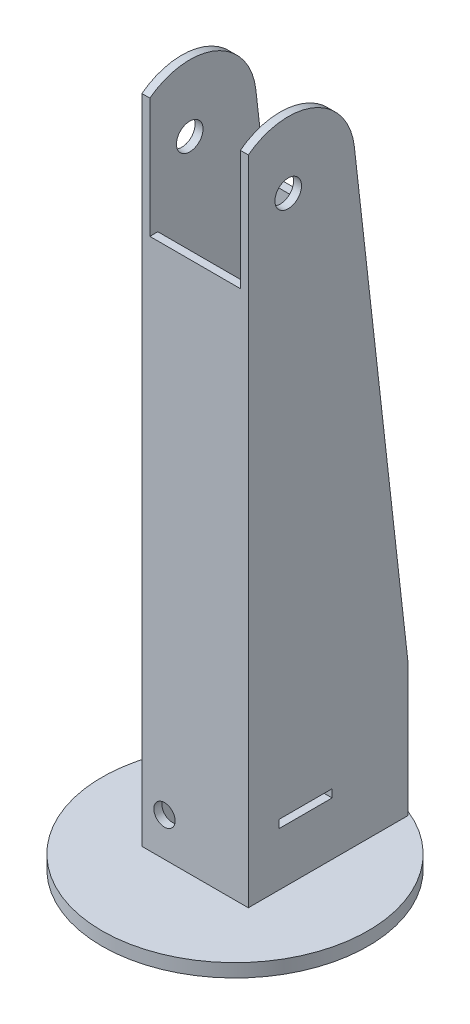
SolidWorks part; units mm, degrees
ref_plane "Alzado" through (0, 0, 0) normal (0, 0, 1) x (1, 0, 0)
ref_plane "Planta" through (0, 0, 0) normal (0, 1, 0) x (1, 0, 0)
ref_plane "Vista lateral" through (0, 0, 0) normal (1, 0, 0) x (0, 0, -1)
sketch "Croquis1" plane through (0, 0, 0) normal (0, 1, 0) x (1, 0, 0)
  line L1 (-20, -30) -> (20, -30)
  line L2 (-20, -30) -> (-20, 30)
  line L3 (-20, 30) -> (20, 30)
  line L4 (20, -30) -> (20, 30)
  line L5 (-20, -30) -> (20, 30) construction
  line L6 (-20, 30) -> (20, -30) construction
  point P0 (0, 0)
  dimension "D1" = 40
  dimension "D2" = 60
extrude "Saliente-Extruir1" add sketch "Croquis1" along normal blind 250
sketch "Croquis2" plane through (0, 250, 0) normal (0, 1, 0) x (1, 0, 0)
  line L0 (-20, -30) -> (20, -30) construction
  line L1 (-17, -30) -> (17, -30)
  line L2 (-17, -30) -> (-17, 30)
  line L3 (-17, 30) -> (17, 30)
  line L4 (17, -30) -> (17, 30)
  line L5 (20, 30) -> (-20, 30) construction
  line L6 (20, -30) -> (20, 30) construction
  line L7 (-20, 30) -> (-20, -30) construction
  dimension "D1" = 3
  dimension "D2" = 3
extrude "Cortar-Extruir1" cut sketch "Croquis2" against normal blind 50
sketch "Croquis3" plane through (20, 0, 0) normal (1, 0, 0) x (0, 0, -1)
  line L0 (-30, 250) -> (-30, 0) construction
  line L1 (-30, 250) -> (30, 250) construction
  circle A0 centre (-15, 225) radius 5
  dimension "D1" = 10
  dimension "D2" = 15
  dimension "D3" = 25
extrude "Cortar-Extruir2" cut sketch "Croquis3" against normal through all
sketch "Croquis5" plane through (20, 0, 0) normal (1, 0, 0) x (0, 0, -1)
  line L0 (30, 50) -> (9.8409, 227.8162)
  line L1 (30, 250) -> (30, 0) construction
  line L3 (-30, 0) -> (30, 0) construction
  line L4 (-30, 250) -> (-30, 0) construction
  arc A0 (9.8409, 227.8162) -> (-30, 245) centre (-15, 225) ccw
  circle A1 centre (-15, 225) radius 5 construction
  line M3 (-30, 250) -> (-30, 0)
  line M5 (30, 0) -> (30, 250)
  line M6 (30, 250) -> (-30, 250)
  dimension "D1" = 25
  dimension "D2" = 50
extrude "Cortar-Extruir5" cut sketch "Croquis5" against normal through all contours A0 L0 M5 M6 | A0 M6 M3 region at (20, 248.5298, 26.3291) region at (20, 186.007, -21.5994)
sketch "Croquis6" plane through (0, 0, 0) normal (0, -1, 0) x (1, 0, 0)
  line L0 (-20, 30) -> (20, 30) construction
  circle A0 centre (0, 15) radius 50
  point P4 (0, 30)
  dimension "D2" = 100
  dimension "D1" = 15
extrude "Saliente-Extruir2" add sketch "Croquis6" along normal blind 5
sketch "Croquis7" plane through (0, 200, 0) normal (0, 1, 0) x (1, 0, 0)
  line L1 (17, -27) -> (-17, -27)
  line L2 (17, -27) -> (17, 10)
  line L3 (17, 10) -> (-17, 10)
  line L4 (-17, -27) -> (-17, 10)
  line L5 (-17, 12.9944) -> (-17, -30) construction
  line L6 (17, -30) -> (17, 12.9944) construction
  line L8 (-17, -30) -> (17, -30) construction
  dimension "D1" = 37
  dimension "D3" = 3
extrude "Cortar-Extruir6" cut sketch "Croquis7" against normal through all
sketch "Croquis8" plane through (0, 0, -30) normal (0, 0, -1) x (-1, 0, 0)
  line L1 (20, 50) -> (20, 0) construction
  line L2 (50, 0) -> (-50, 0) construction
  circle A0 centre (11.5, 14.5) radius 4
  dimension "D1" = 8
  dimension "D2" = 14.5
  dimension "D3" = 8.5
extrude "Cortar-Extruir7" cut sketch "Croquis8" against normal through all
sketch "Croquis10" plane through (-20, 0, 0) normal (-1, 0, 0) x (0, 0, 1)
  line L0 (-30, 0) -> (30, 0) construction
  line L1 (-1.5, 20) -> (18.5, 20)
  line L2 (-1.5, 20) -> (-1.5, 23)
  line L3 (-1.5, 23) -> (18.5, 23)
  line L4 (18.5, 20) -> (18.5, 23)
  line L5 (-1.5, 20) -> (18.5, 23) construction
  line L6 (-1.5, 23) -> (18.5, 20) construction
  line L8 (30, 245) -> (30, 0) construction
  point P0 (8.5, 21.5)
  dimension "D1" = 20
  dimension "D2" = 3
  dimension "D3" = 20
  dimension "D4" = 21.5
extrude "Cortar-Extruir8" cut sketch "Croquis10" against normal through all
